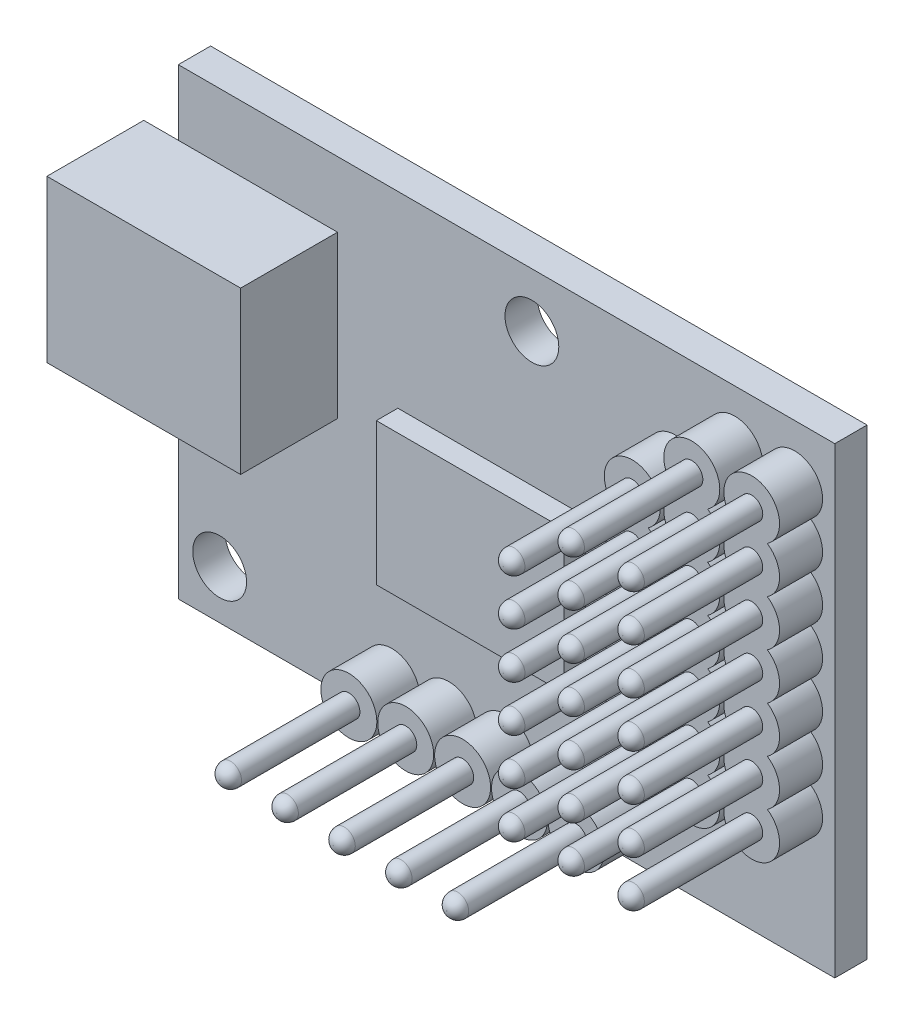
SolidWorks part; units mm, degrees
ref_plane "Plan de face" through (0, 0, 0) normal (0, 0, 1) x (1, 0, 0)
ref_plane "Plan de dessus" through (0, 0, 0) normal (0, 1, 0) x (1, 0, 0)
ref_plane "Plan de droite" through (0, 0, 0) normal (1, 0, 0) x (0, 0, -1)
sketch "Esquisse1" plane through (0, 0, 0) normal (0, 0, 1) x (1, 0, 0)
  line L1 (15.25, -10.75) -> (-15.25, -10.75)
  line L2 (15.25, -10.75) -> (15.25, 10.75)
  line L3 (15.25, 10.75) -> (-15.25, 10.75)
  line L4 (-15.25, -10.75) -> (-15.25, 10.75)
  line L7 (-16.8554, 7.7059) -> (-7.8554, 7.7059)
  line L8 (-16.8554, 7.7059) -> (-16.8554, 0.2059)
  line L9 (-16.8554, 0.2059) -> (-7.8554, 0.2059)
  line L10 (-7.8554, 7.7059) -> (-7.8554, 0.2059)
  circle A0 centre (-5.3268, -9.0787) radius 1.3
  circle A1 centre (10.6056, 8.2359) radius 0.5135
  circle A2 centre (13.3893, 8.2359) radius 0.5135
  circle A3 centre (7.8414, 6.0959) radius 0.5135
  circle A4 centre (10.6056, 6.0959) radius 0.5135
  circle A5 centre (13.3893, 6.0959) radius 0.5135
  circle A6 centre (7.8414, 3.9559) radius 0.5135
  circle A7 centre (10.6056, 3.9559) radius 0.5135
  circle A8 centre (13.3893, 3.9559) radius 0.5135
  circle A9 centre (7.8414, 1.8159) radius 0.5135
  circle A10 centre (10.6056, 1.8159) radius 0.5135
  circle A11 centre (13.3893, 1.8159) radius 0.5135
  circle A12 centre (7.8414, -0.3241) radius 0.5135
  circle A13 centre (10.6056, -0.3241) radius 0.5135
  circle A14 centre (13.3893, -0.3241) radius 0.5135
  circle A15 centre (7.8414, -2.4641) radius 0.5135
  circle A16 centre (10.6056, -2.4641) radius 0.5135
  circle A17 centre (13.3893, -2.4641) radius 0.5135
  circle A18 centre (7.8414, -4.6041) radius 0.5135
  circle A19 centre (10.6056, -4.6041) radius 0.5135
  circle A20 centre (13.3893, -4.6041) radius 0.5135
  circle A21 centre (-13.3306, -8.4881) radius 1.25
  circle A22 centre (2.6, -9.0796) radius 0.5135
  circle A23 centre (-2.6846, -9.0886) radius 0.5135
  circle A24 centre (-5.3268, -9.0787) radius 0.5135
  circle A25 centre (-0.0419, -9.0835) radius 0.5135
  circle A26 centre (5.2287, -9.0693) radius 0.5135
  circle A27 centre (1.1766, 8.2359) radius 1.25
  arc A28 (8.5798, 5.0259) -> (7.1031, 5.0259) centre (7.8414, 6.0959) ccw
  arc A29 (11.3439, 5.0259) -> (11.3439, 7.1659) centre (10.6056, 6.0959) ccw
  arc A30 (14.116, 5.0259) -> (14.116, 7.1659) centre (13.3893, 6.0959) ccw
  arc A31 (7.1031, 5.0259) -> (7.1031, 2.8859) centre (7.8414, 3.9559) ccw
  arc A32 (12.6627, 5.0259) -> (12.6627, 2.8859) centre (13.3893, 3.9559) ccw
  arc A33 (9.8673, 5.0259) -> (9.8673, 2.8859) centre (10.6056, 3.9559) ccw
  arc A34 (9.8673, 0.7459) -> (9.8673, -1.3941) centre (10.6056, -0.3241) ccw
  arc A35 (12.6627, 0.7459) -> (12.6627, -1.3941) centre (13.3893, -0.3241) ccw
  arc A36 (7.1031, 0.7459) -> (7.1031, -1.3941) centre (7.8414, -0.3241) ccw
  arc A37 (8.5798, 0.7459) -> (8.5798, 2.8859) centre (7.8414, 1.8159) ccw
  arc A38 (14.116, 0.7459) -> (14.116, 2.8859) centre (13.3893, 1.8159) ccw
  arc A39 (11.3439, 0.7459) -> (11.3439, 2.8859) centre (10.6056, 1.8159) ccw
  arc A40 (9.8673, -3.5341) -> (11.3439, -3.5341) centre (10.6056, -4.6041) ccw
  arc A41 (12.6627, -3.5341) -> (14.116, -3.5341) centre (13.3893, -4.6041) ccw
  arc A42 (7.1031, -3.5341) -> (8.5798, -3.5341) centre (7.8414, -4.6041) ccw
  arc A43 (8.5798, -3.5341) -> (8.5798, -1.3941) centre (7.8414, -2.4641) ccw
  arc A44 (14.116, -3.5341) -> (14.116, -1.3941) centre (13.3893, -2.4641) ccw
  arc A45 (11.3439, -3.5341) -> (11.3439, -1.3941) centre (10.6056, -2.4641) ccw
  arc A46 (14.116, 7.1659) -> (12.6627, 7.1659) centre (13.3893, 8.2359) ccw
  arc A47 (11.3439, 7.1659) -> (9.8673, 7.1659) centre (10.6056, 8.2359) ccw
  arc A48 (7.1031, 2.8859) -> (7.1031, 0.7459) centre (7.8414, 1.8159) ccw
  arc A49 (8.5798, 2.8859) -> (8.5798, 5.0259) centre (7.8414, 3.9559) ccw
  arc A50 (7.1031, -1.3941) -> (7.1031, -3.5341) centre (7.8414, -2.4641) ccw
  arc A51 (8.5798, -1.3941) -> (8.5798, 0.7459) centre (7.8414, -0.3241) ccw
  arc A52 (11.3439, -1.3941) -> (11.3439, 0.7459) centre (10.6056, -0.3241) ccw
  arc A53 (9.8673, -1.3941) -> (9.8673, -3.5341) centre (10.6056, -2.4641) ccw
  arc A54 (11.3439, 2.8859) -> (11.3439, 5.0259) centre (10.6056, 3.9559) ccw
  arc A55 (9.8673, 2.8859) -> (9.8673, 0.7459) centre (10.6056, 1.8159) ccw
  arc A56 (9.8673, 7.1659) -> (9.8673, 5.0259) centre (10.6056, 6.0959) ccw
  arc A57 (12.6627, 7.1659) -> (12.6627, 5.0259) centre (13.3893, 6.0959) ccw
  arc A58 (14.116, 2.8859) -> (14.116, 5.0259) centre (13.3893, 3.9559) ccw
  arc A59 (12.6627, 2.8859) -> (12.6627, 0.7459) centre (13.3893, 1.8159) ccw
  arc A60 (14.116, -1.3941) -> (14.116, 0.7459) centre (13.3893, -0.3241) ccw
  arc A61 (12.6627, -1.3941) -> (12.6627, -3.5341) centre (13.3893, -2.4641) ccw
  circle A62 centre (5.2287, -9.0693) radius 1.3
  circle A63 centre (2.6, -9.0796) radius 1.3
  circle A64 centre (-0.0419, -9.0835) radius 1.3
  circle A65 centre (-2.6846, -9.0886) radius 1.3
extrude "Boss.-Extru.6" add sketch "Esquisse1" along normal blind 9.5 contours A3 | A6 | A9 | A12 | A15 | A18 | A19 | A16 | A13 | A10 | A7 | A4 | A1 | A20 | A17 | A14 | A11 | A8 | A5 | A2 | A24 | A23 | A25 | A22 | A26 region at (10.6056, 8.2359, 0) region at (13.3893, 8.2359, 0) region at (7.8414, 6.0959, 0) region at (10.6056, 6.0959, 0) region at (13.3893, 6.0959, 0) region at (7.8414, 3.9559, 0) region at (10.6056, 3.9559, 0) region at (13.3893, 3.9559, 0) region at (7.8414, 1.8159, 0) region at (10.6056, 1.8159, 0) region at (13.3893, 1.8159, 0) region at (7.8414, -0.3241, 0) region at (10.6056, -0.3241, 0) region at (13.3893, -0.3241, 0) region at (7.8414, -2.4641, 0) region at (10.6056, -2.4641, 0) region at (13.3893, -2.4641, 0) region at (7.8414, -4.6041, 0) region at (10.6056, -4.6041, 0) region at (13.3893, -4.6041, 0) region at (2.6, -9.0796, 0) region at (-2.6846, -9.0886, 0) region at (-5.3268, -9.0787, 0) region at (-0.0419, -9.0835, 0) region at (5.2287, -9.0693, 0)
extrude "Boss.-Extru.7" add sketch "Esquisse1<3>" along normal blind 3.5 contours A0 A24 | A65 A23 | A64 A25 | A63 A22 | A62 A26 | A35 A61 A41 A44 A60 A38 A58 A30 A46 A57 A32 A59 A2 A5 A8 A11 A14 A17 A20 | A47 A56 A33 A55 A34 A53 A40 A45 A52 A39 A54 A29 A1 A4 A7 A10 A13 A16 A19 | A43 A51 A37 A49 A28 A31 A48 A36 A50 A42 A3 A6 A9 A12 A15 A18 region at (-6.59, -9.0787, 0) region at (7.8414, 0.7459, 0) region at (11.749, 3.9559, 0) region at (14.5263, 3.9559, 0) region at (3.9655, -9.0693, 0) region at (1.3368, -9.0796, 0) region at (-1.3051, -9.0835, 0) region at (-3.9478, -9.0886, 0)
sketch "Esquisse1<3>" plane through (0, 0, 0) normal (0, 0, 1) x (1, 0, 0) same geometry as "Esquisse1"
extrude "Boss.-Extru.8" add sketch "Esquisse1<4>" along normal blind 1.5 contours L7 L10 L9 L4 L1 L2 L3 A65 A64 A63 A62 A61 A35 A59 A32 A57 A46 A30 A58 A38 A60 A44 A41 A56 A47 A29 A54 A39 A52 A45 A40 A53 A34 A55 A33 A51 A43 A42 A50 A36 A48 A31 A28 region at (-0.7558, -0.2653, 0)
sketch "Esquisse1<4>" plane through (0, 0, 0) normal (0, 0, 1) x (1, 0, 0) same geometry as "Esquisse1"
extrude "Boss.-Extru.9" add sketch "Esquisse1<5>" along normal blind 6 contours L8 L9 L4 L7 | L10 L7 L4 L9 region at (-16.0527, 3.9559, 0) region at (-11.5527, 3.9559, 0)
sketch "Esquisse1<5>" plane through (0, 0, 0) normal (0, 0, 1) x (1, 0, 0) same geometry as "Esquisse1"
sketch "Esquisse2" plane through (0, 7.7059, 0) normal (0, 1, 0) x (1, 0, 0)
  line L1 (-16.8554, 0) -> (-15.25, 0)
  line L2 (-16.8554, 0) -> (-16.8554, -1.5)
  line L3 (-16.8554, -1.5) -> (-15.25, -1.5)
  line L4 (-15.25, 0) -> (-15.25, -1.5)
extrude "Enlèv. mat.-Extru.1" cut sketch "Esquisse2" against normal blind 10
fillet "Congé1" radius 0.5 25 edges at (13.9029, 1.8159, 9.5) (-4.8133, -9.0787, 9.5) (-2.171, -9.0886, 9.5) (0.4716, -9.0835, 9.5) (3.1135, -9.0796, 9.5) (5.7422, -9.0693, 9.5) (13.9029, -4.6041, 9.5) (13.9029, -2.4641, 9.5) (11.1191, -2.4641, 9.5) (11.1191, -4.6041, 9.5) (8.355, -4.6041, 9.5) (8.355, -2.4641, 9.5) (8.355, -0.3241, 9.5) (11.1191, -0.3241, 9.5) (13.9029, -0.3241, 9.5) (13.9029, 3.9559, 9.5) (11.1191, 1.8159, 9.5) (8.355, 1.8159, 9.5) (8.355, 3.9559, 9.5) (11.1191, 3.9559, 9.5) (11.1191, 6.0959, 9.5) (13.9029, 6.0959, 9.5) (13.9029, 8.2359, 9.5) (11.1191, 8.2359, 9.5) (8.355, 6.0959, 9.5)
sketch "Esquisse3" plane through (-16.8554, 0, 0) normal (-1, 0, 0) x (0, 0, 1)
  line L0 (5.5071, 7.01) -> (5.5071, 0.7534)
  line L1 (5.5071, 0.7534) -> (4.2115, 0.7534)
  line L2 (4.2115, 0.7534) -> (3.1674, 1.8112)
  line L3 (3.1674, 1.8112) -> (2.1171, 1.8112)
  line L4 (2.1171, 1.8112) -> (2.1171, 5.9952)
  line L5 (2.1171, 5.9952) -> (3.1674, 5.9952)
  line L6 (3.1674, 5.9952) -> (4.2115, 7.0257)
  line L7 (4.2115, 7.0257) -> (5.5071, 7.01)
  line L9 (3.5801, 5.6067) -> (2.7548, 5.6067)
  line L10 (3.5801, 5.6067) -> (3.5801, 2.1364)
  line L11 (3.5801, 2.1364) -> (2.7548, 2.1364)
  line L12 (2.7548, 5.6067) -> (2.7548, 2.1364)
  line L13 (3.5801, 5.6067) -> (2.7548, 2.1364) construction
  line L14 (3.5801, 2.1364) -> (2.7548, 5.6067) construction
  point P2 (3.1674, 3.8715)
extrude "Enlèv. mat.-Extru.2" cut sketch "Esquisse3" against normal blind 8
sketch "Esquisse4" plane through (0, 0, 1.5) normal (0, 0, 1) x (1, 0, 0)
  line L1 (-5.0514, 2.0265) -> (3.6783, 2.0265)
  line L2 (-5.0514, 2.0265) -> (-5.0514, -4.5778)
  line L3 (-5.0514, -4.5778) -> (3.6783, -4.5778)
  line L4 (3.6783, 2.0265) -> (3.6783, -4.5778)
  line L5 (-5.0514, 2.0265) -> (3.6783, -4.5778) construction
  line L6 (-5.0514, -4.5778) -> (3.6783, 2.0265) construction
  point P0 (-0.6866, -1.2757)
extrude "Boss.-Extru.10" add sketch "Esquisse4" along normal blind 1
